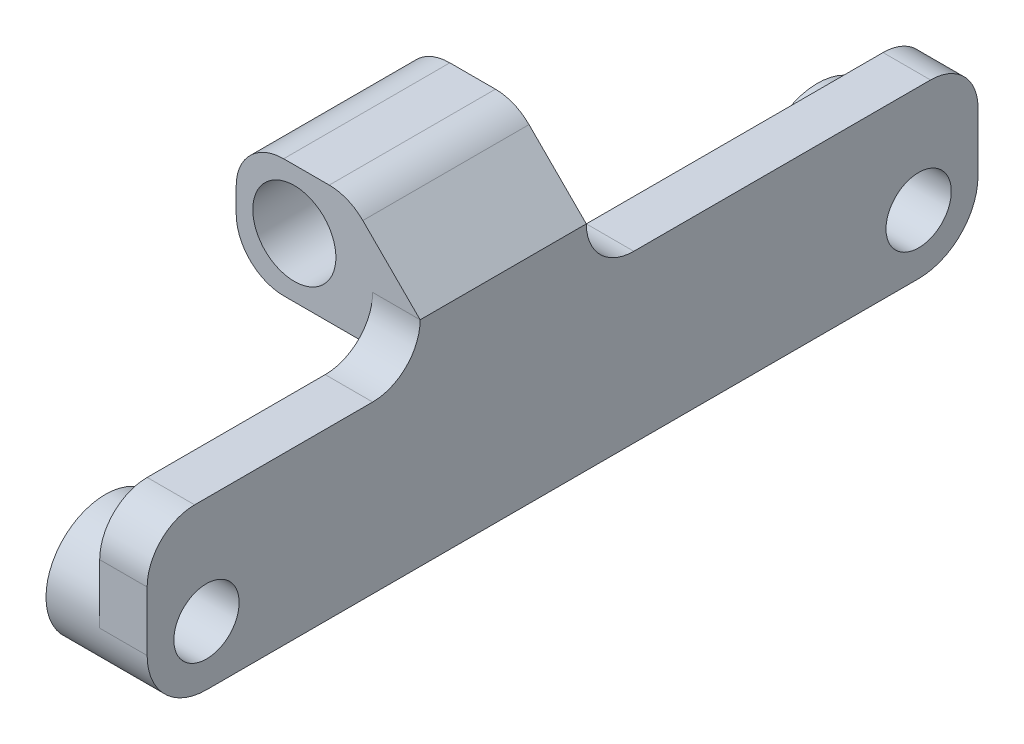
SolidWorks part; units mm, degrees
ref_plane "Front Plane" through (0, 0, 0) normal (0, 0, 1) x (1, 0, 0)
ref_plane "Top Plane" through (0, 0, 0) normal (0, 1, 0) x (1, 0, 0)
ref_plane "Right Plane" through (0, 0, 0) normal (1, 0, 0) x (0, 0, -1)
sketch "Sketch1" plane through (0, 0, 0) normal (1, 0, 0) x (0, 0, -1)
  circle A0 centre (30, 0) radius 5
  circle A1 centre (-30, 0) radius 5
  dimension "D1" = 2
extrude "Boss-Extrude1" add sketch "Sketch1" along normal blind 5.1
sketch "Sketch2" plane through (5.1, 0, 0) normal (1, 0, 0) x (0, 0, -1)
  line L1 (30, -5) -> (-30, -5)
  line L3 (-35, 0) -> (-35, 5)
  line L4 (-35, 5) -> (-35, 9)
  line L6 (35, 9) -> (35, 0)
  line L8 (35, 9) -> (-35, 9)
  circle A0 centre (-30, 0) radius 5 construction
  circle A1 centre (30, 0) radius 5 construction
  arc A2 (-35, 0) -> (-30, -5) centre (-30, 0) ccw
  arc A3 (30, -5) -> (35, 0) centre (30, 0) ccw
extrude "Boss-Extrude2" add sketch "Sketch2" along normal blind 4
sketch "Sketch3" plane through (0, 9, 0) normal (0, 1, 0) x (1, 0, 0)
  line L2 (5.1, 2) -> (-4.9, 2)
  line L3 (-4.9, 2) -> (-6.4, 2)
  line L4 (9.1, 2) -> (5.1, 2)
  line L6 (-4.9, -12) -> (9.1, -12)
  line L8 (9.1, -12) -> (9.1, 2)
  line L10 (-6.4, -12) -> (-4.9, -12)
  line L12 (-6.4, -12) -> (-6.4, 2)
extrude "Boss-Extrude3" add sketch "Sketch3" along normal blind 4
sketch "Sketch4" plane through (0, 13, 0) normal (0, 1, 0) x (1, 0, 0)
  line L8 (9.1, 2) -> (-6.4, 2) construction
  line L9 (3.1, 2) -> (-6.4, 2)
  line L16 (-6.4, -12) -> (9.1, -12) construction
  line L17 (3.1, -12) -> (3.1, 2)
  line L18 (3.1, -12) -> (-6.4, -12)
  line L20 (-6.4, -12) -> (-6.4, 2)
  point P3 (3.8953, 15)
extrude "Boss-Extrude4" add sketch "Sketch4" along normal blind 6
sketch "Sketch5" plane through (0, 0, -2) normal (0, 0, 1) x (1, 0, 0)
  circle A0 centre (-1.5, 14) radius 3.5
extrude "Cut-Extrude1" cut sketch "Sketch5" along normal through all
sketch "Sketch6" plane through (0, 0, -2) normal (0, 0, -1) x (-1, 0, 0)
  line L1 (1.5, 9) -> (5.8301, 11.5)
  line L2 (5.8301, 11.5) -> (5.8301, 16.5)
  line L3 (5.8301, 16.5) -> (1.5, 19)
  line L4 (1.5, 19) -> (-2.8301, 16.5)
  line L5 (-2.8301, 16.5) -> (-2.8301, 11.5)
  line L6 (-2.8301, 11.5) -> (1.5, 9)
  circle A0 centre (1.5, 14) radius 5 construction
sketch "Sketch7" plane through (0, 0, 0) normal (-1, 0, 0) x (0, 0, 1)
  circle A0 centre (-30, 0) radius 2.75
  circle A1 centre (30, 0) radius 2.75
extrude "Cut-Extrude2" cut sketch "Sketch7" against normal through all
sketch "Sketch8" plane through (0, 0, -2) normal (0, 0, -1) x (-1, 0, 0)
  line L0 (-9.1, 13) -> (-3.1, 19)
  line L1 (-3.1, 19) -> (-3.1, 13)
  line L2 (-3.1, 13) -> (-9.1, 13)
extrude "Boss-Extrude5" add sketch "Sketch8" against normal up to surface (14 mm away) up to face at (-5, 14, 12)
fillet "Fillet1" radius 4 3 edges at (-6.4, 9, 5) (-6.4, 19, 5) (3.1, 19, 5)
fillet "Fillet2" radius 4 2 edges at (7.1, 9, 12) (7.1, 9, -2)
fillet "Fillet3" radius 4 2 edges at (7.1, 9, -35) (7.1, 9, 35)
chamfer "Chamfer1" distance 1 angle 30 2 edges at (0, 0, 25) (0, 0, -35) first distance on face at (0, 0, 32.75) first distance on face at (0, 0, -27.25)
